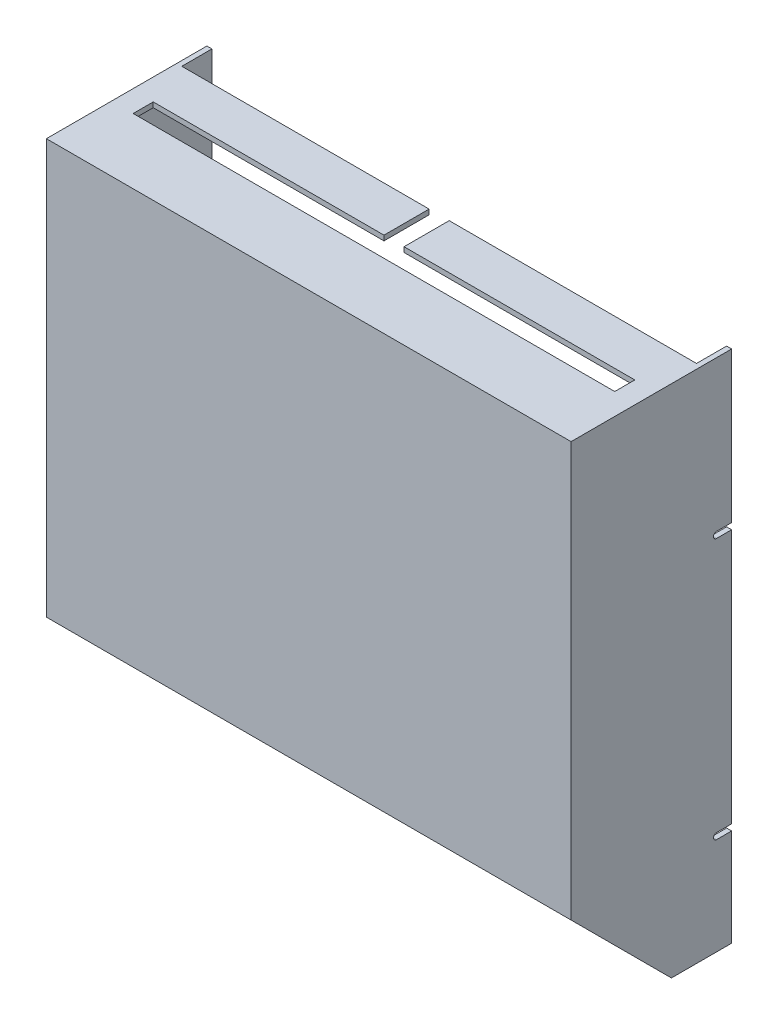
SolidWorks part; units mm, degrees
material "ABS PC generico"
ref_plane "Piano frontale" through (0, 0, 0) normal (0, 0, 1) x (1, 0, 0)
ref_plane "Piano superiore" through (0, 0, 0) normal (0, 1, 0) x (1, 0, 0)
ref_plane "Piano destro" through (0, 0, 0) normal (1, 0, 0) x (0, 0, -1)
sketch "Schizzo1" plane through (0, 0, 0) normal (0, 0, 1) x (1, 0, 0)
  line L0 (-200, -200) -> (-200, 200) construction
  line L1 (-230, -230) -> (230, -230) construction
  line L2 (-230, -230) -> (-230, 230) construction
  line L3 (-230, 230) -> (230, 230) construction
  line L4 (230, -230) -> (230, 230) construction
  line L5 (-230, -230) -> (230, 230) construction
  line L6 (-230, 230) -> (230, -230) construction
  line L7 (-200, 200) -> (200, 200) construction
  line L8 (200, -200) -> (200, 200) construction
  line L9 (-200, -200) -> (200, -200) construction
  point P0 (0, 0)
  dimension "D1" = 460
  dimension "D2" = 460
  dimension "D3" = 30
sketch "Schizzo2" plane through (0, 0, 0) normal (0, 0, 1) x (1, 0, 0)
  line L0 (-235, -230) -> (-235, 283)
  line L1 (288, -230) -> (-235, -230)
  line L2 (283, -225) -> (283, 278) construction
  line L3 (288, 283) -> (-235, 283)
  line L4 (-230, -225) -> (-230, 278) construction
  line L7 (288, -230) -> (288, 283)
  line L8 (283, 278) -> (-230, 278) construction
  line L9 (283, -225) -> (-230, -225) construction
  line L10 (283, -230) -> (-230, -230) construction
  line L11 (-230, -230) -> (-230, 283) construction
  line L12 (283, 283) -> (-230, 283) construction
  line L13 (283, -230) -> (283, 283) construction
  point P0 (0, 0)
  dimension "D1" = 523
  dimension "D2" = 513
  dimension "D3" = 5
  dimension "D4" = 5
  dimension "D5" = 5
  dimension "D6" = 5
extrude "Estrusione-Estrusione2" add sketch "Schizzo2" along normal blind 130
shell "Svuota1" thickness 5 removed face at (26.5, 26.5, 0)
sketch "Schizzo3" plane through (288, 0, 0) normal (1, 0, 0) x (0, 0, -1)
  line L0 (0, -311.6614) -> (0, 309.1506) construction
  line L1 (-30, -311.6614) -> (-30, 309.1506) construction
  line L2 (-130, -130) -> (-30, -230)
  line L3 (-130, -230) -> (-30, -230)
  line L4 (-130, -230) -> (-130, -130)
  line L5 (-130, -130) -> (-30, -130) construction
  line L6 (-30, -230) -> (-30, -130) construction
  line L7 (-130, -122.9289) -> (-22.9289, -230)
  line L8 (-30, -230) -> (-22.9289, -230)
  line L9 (-130, -130) -> (-130, -122.9289)
  line L11 (-126.4645, -126.4645) -> (-20.4648, -232.4641) construction
  line L14 (-130, -130) -> (-24.0003, -235.9997) construction
  line M3 (-130, 283) -> (-130, -230)
  line M4 (-130, -230) -> (0, -230)
  dimension "D2" = 100
  dimension "D3" = 100
  dimension "D5" = 7.0711
  dimension "D6" = 7.0711
  dimension "D1" = 30
  dimension "D4" = 5
extrude "Taglio-Estrusione2" cut sketch "Schizzo3" against normal up to surface (523 mm away) contours L2 M3 M4 region at (288, -196.6667, 96.6667) up to face at (-235, 26.5, 65)
extrude "Estrusione-Estrusione3" add sketch "Schizzo3<4>" against normal up to surface (523 mm away) contours L7 L2 M3 M4 region at (288, -178.2121, 78.2121) up to face at (-235, -4.8, 58)
sketch "Schizzo3<4>" plane through (288, 0, 0) normal (1, 0, 0) x (0, 0, -1) same geometry as "Schizzo3"
sketch "Schizzo4" plane through (0, 283, 0) normal (0, 1, 0) x (1, 0, 0)
  line L0 (26.5, 0) -> (26.5, -65) construction
  line L1 (-213.5, -65) -> (266.5, -65)
  line L2 (26.5, 0) -> (26.5, 95.6986) construction
  line L3 (288, 0) -> (-235, 0) construction
  line L4 (16.5, 0) -> (16.5, -45)
  line L5 (-213.5, -45) -> (16.5, -45)
  line L6 (36.5, 0) -> (16.5, 0)
  line L8 (-213.5, -45) -> (-213.5, -65)
  line L10 (266.5, -45) -> (266.5, -65)
  line L14 (266.5, -45) -> (36.5, -45)
  line L15 (36.5, 0) -> (36.5, -45)
  point P0 (0, 92.1723)
  point P1 (0, -193.3013)
  point P2 (-235, -65)
  point P3 (235, -65)
  point P8 (-10, 92.1723)
  point P9 (-10, -193.3013)
  point P10 (-235, -45)
  point P11 (235, -45)
  dimension "D3" = 230
extrude "Taglio-Estrusione3" cut sketch "Schizzo4" against normal blind 10
sketch "Schizzo5" plane through (0, 0, 0) normal (0, 0, 1) x (1, 0, 0)
  line L0 (283, -230) -> (288, -230)
  line L12 (16.5, 278) -> (16.5, 283)
  line L13 (-230, 278) -> (16.5, 278)
  line L14 (-230, -225) -> (-230, 278)
  line L15 (283, -225) -> (-230, -225)
  line L16 (283, 278) -> (283, -225)
  line L17 (36.5, 278) -> (283, 278)
  line L18 (36.5, 283) -> (36.5, 278)
  line L19 (288, 283) -> (36.5, 283)
  line L20 (288, -230) -> (288, 283)
  line L21 (-235, -230) -> (288, -230)
  line L22 (-235, 283) -> (-235, -230)
  line L23 (16.5, 283) -> (-235, 283)
  line L26 (-230, -230) -> (-230, 283)
  line L28 (283, 283) -> (283, -230)
  line L31 (288, 283) -> (283, 283)
  line L32 (288, -230) -> (288, 283)
  line L33 (-235, -230) -> (-230, -230)
  line L34 (-235, 283) -> (-235, -230)
  line L35 (-230, 283) -> (-235, 283)
  dimension "D1" = 0
extrude "Estrusione-Estrusione5" add sketch "Schizzo5" against normal blind 30
sketch "Schizzo6" plane through (-235, 0, 0) normal (-1, 0, 0) x (0, 0, 1)
  line L0 (0, 252.5489) -> (0, -248.8531) construction
  line L1 (-15, 252.5489) -> (-15, -248.8531) construction
  line L2 (-224.7552, 0) -> (0, 0) construction
  line L3 (-224.7552, -130) -> (0, -130) construction
  line L4 (-224.7552, 130) -> (0, 130) construction
  line L5 (-15, 133.05) -> (-30, 133.05)
  line L6 (-224.7552, 130) -> (336.9736, 130) construction
  line L7 (-224.7552, -130) -> (336.9736, -130) construction
  line L8 (-224.7552, 0) -> (336.9736, 0) construction
  line L9 (-15, 126.95) -> (-30, 126.95)
  line L10 (-30, 133.05) -> (-30, 126.95)
  line L12 (-30, -133.05) -> (-30, -126.95)
  line L13 (-15, -126.95) -> (-30, -126.95)
  line L14 (-15, -133.05) -> (-30, -133.05)
  arc A0 (-15, 126.95) -> (-15, 133.05) centre (-15, 130) ccw
  arc A1 (-15, -126.95) -> (-15, -133.05) centre (-15, -130) cw
  dimension "D4" = 3.05
  dimension "D1" = 15
  dimension "D2" = 130
  dimension "D3" = 130
extrude "Taglio-Estrusione4" cut sketch "Schizzo6" against normal up to surface (523 mm away) up to face at (288, -4.8, 46)
